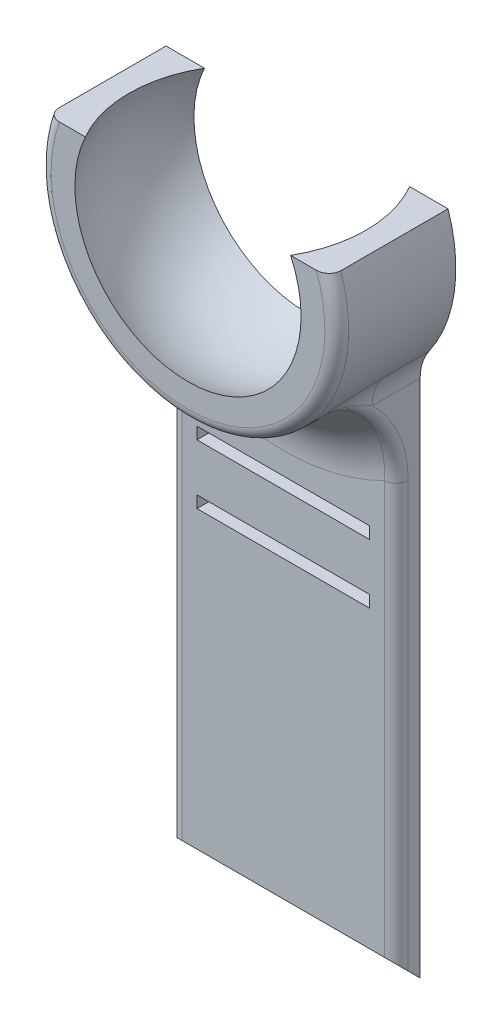
SolidWorks part; units mm, degrees
ref_plane "Front Plane" through (0, 0, 0) normal (0, 0, 1) x (1, 0, 0)
ref_plane "Top Plane" through (0, 0, 0) normal (0, 1, 0) x (1, 0, 0)
ref_plane "Right Plane" through (0, 0, 0) normal (1, 0, 0) x (0, 0, -1)
sketch "Sketch1" plane through (0, 0, 0) normal (0, 0, 1) x (1, 0, 0)
  line L1 (9.5, -22.5) -> (-9.5, -22.5)
  line L2 (9.5, -22.5) -> (9.5, 22.5)
  line L3 (9.5, 22.5) -> (-9.5, 22.5)
  line L4 (-9.5, -22.5) -> (-9.5, 22.5)
  line L5 (9.5, -22.5) -> (-9.5, 22.5) construction
  line L6 (9.5, 22.5) -> (-9.5, -22.5) construction
  point P0 (0, 0)
  dimension "D1" = 19
  dimension "D2" = 45
extrude "Boss-Extrude1" add sketch "Sketch1" along normal blind 2
sketch "Sketch4" plane through (0, 0, 0) normal (0, 0, -1) x (-1, 0, 0)
  line L0 (-11.8427, 34.624) -> (-8.6168, 34.624)
  line L1 (0, 30.624) -> (-50000, 30.624) construction
  line L2 (8.6168, 34.624) -> (11.8427, 34.624)
  arc A0 (-8.6168, 34.624) -> (8.6168, 34.624) centre (0, 30.624) ccw
  arc A1 (-11.8427, 34.624) -> (11.8427, 34.624) centre (0, 30.624) ccw
  circle A2 centre (0, 30.624) radius 12.5 construction
  circle A3 centre (0, 30.624) radius 9.5 construction
  point P10 (0, 51.2973)
  dimension "D1" = 19
  dimension "D3" = 4
  dimension "D2" = 3
extrude "Boss-Extrude5" add sketch "Sketch4" against normal blind 10
sketch "Sketch5" plane through (0, 0, 2) normal (0, 0, 1) x (1, 0, 0)
  line L1 (4.9244, 22.5) -> (-4.9244, 22.5)
  line L14 (4.9244, 22.5) -> (-4.9244, 22.5)
  arc A1 (-4.9244, 22.5) -> (4.9244, 22.5) centre (0, 30.624) ccw
  arc A12 (-4.9244, 22.5) -> (4.9244, 22.5) centre (0, 30.624) ccw
  dimension "D1" = 0
extrude "Cut-Extrude1" cut sketch "Sketch5" against normal up to next
ref_plane "Plane2" through (0, 30.624, 0) normal (0, 1, 0) x (1, 0, 0)
sketch "Sketch9" plane through (0, 30.624, 0) normal (0, 1, 0) x (1, 0, 0)
  line L1 (0, -7.5) -> (0, 49992.5) construction
  line L3 (9.5, -10) -> (9.5, 0)
  line L4 (9.5, 0) -> (-9.5, 0) construction
  line L5 (-9.5, -10) -> (9.5, -10) construction
  arc A1 (9.5, 0) -> (9.5, -10) centre (0, -5) cw
revolve "Cut-Revolve1" cut sketch "Sketch9" angle 360 about L1
fillet "Fillet1" radius 6 1 edges at (0, 18.124, 2)
fillet "Fillet4" radius 1 5 edges at (9.5, 21.3776, 5.0828) (-9.5, -3.8752, 2) (9.5, -3.8752, 2) (-9.5, 20.2791, 3.9807) (0, 18.124, 10)
fillet "Fillet5" radius 4 4 edges at (9.3294, 22.3046, 7.6498) (-9.3284, 22.3036, 7.6539) (9.5, 22.5, 3.0586) (-9.5, 22.5, 3.0586)
sketch "Sketch10" plane through (0, 0, 2) normal (0, 0, 1) x (1, 0, 0)
  line L1 (7.25, 9.2734) -> (-7.25, 9.2734)
  line L2 (7.25, 9.2734) -> (7.25, 10.2734)
  line L3 (7.25, 10.2734) -> (-7.25, 10.2734)
  line L4 (-7.25, 9.2734) -> (-7.25, 10.2734)
  line L5 (7.25, 9.2734) -> (-7.25, 10.2734) construction
  line L6 (7.25, 10.2734) -> (-7.25, 9.2734) construction
  line L7 (7.25, 4.2734) -> (-7.25, 4.2734)
  line L8 (7.25, 4.2734) -> (7.25, 5.2734)
  line L9 (7.25, 5.2734) -> (-7.25, 5.2734)
  line L10 (-7.25, 4.2734) -> (-7.25, 5.2734)
  line L11 (7.25, 4.2734) -> (-7.25, 5.2734) construction
  line L12 (7.25, 5.2734) -> (-7.25, 4.2734) construction
  point P0 (0, 9.7734)
  point P5 (0, 4.7734)
  dimension "D1" = 14.5
  dimension "D2" = 1
  dimension "D3" = 1
  dimension "D4" = 14.5
  dimension "D5" = 4
extrude "Cut-Extrude2" cut sketch "Sketch10" against normal up to next
sketch "Sketch11" plane through (9.5, 0, 0) normal (1, 0, 0) x (0, 0, -1)
  line L0 (0, -22.5) -> (-2, -20.5)
  line L1 (-2, -20.5) -> (-2, -22.5)
  line L2 (-2, -22.5) -> (0, -22.5)
  line L3 (-2, -22.5) -> (-2, 14.1924) construction
  point P3 (-2, -20.4983)
  dimension "D1" = 45
extrude "Cut-Extrude3" cut sketch "Sketch11" against normal up to next
